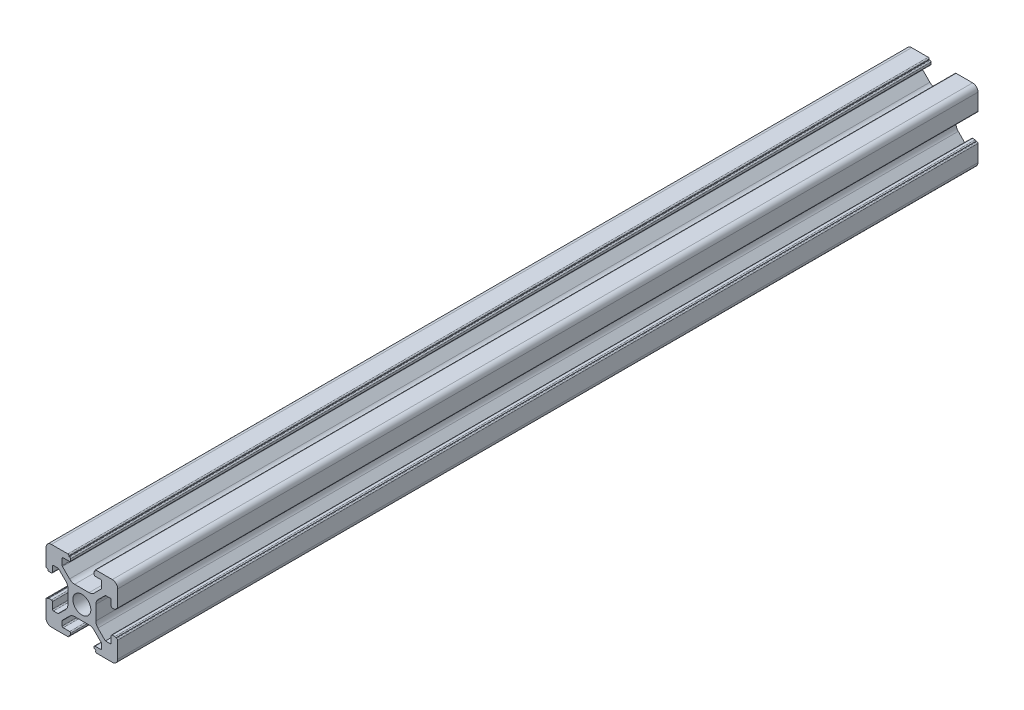
SolidWorks part; units mm, degrees
ref_plane "Front Plane" through (0, 0, 0) normal (0, 0, 1) x (1, 0, 0)
ref_plane "Top Plane" through (0, 0, 0) normal (0, 1, 0) x (1, 0, 0)
ref_plane "Right Plane" through (0, 0, 0) normal (1, 0, 0) x (0, 0, -1)
sketch "Model" plane through (0, 0, 0) normal (0, 0, 1) x (1, 0, 0)
  line L0 (3.9, -0.3) -> (3.9, -2.3109)
  line L1 (4.4858, -3.7251) -> (6.5607, -5.8)
  line L2 (6.5607, -5.8) -> (7.9, -5.8)
  line L3 (8.2, -5.5) -> (8.2, -3.7)
  line L4 (8.5, -3.4) -> (9.2, -3.4)
  line L5 (9.5, -3.7) -> (9.5, -3.6)
  line L6 (9.5, -3.6) -> (9.7, -3.6)
  line L7 (10, -3.9) -> (10, -8.5)
  line L8 (8.5, -10) -> (4.1583, -10)
  line L9 (3.4, -9) -> (3.4, -8.8)
  line L10 (3.7, -8.5) -> (5.2, -8.5)
  line L11 (5.5, -8.2) -> (5.5, -6.9849)
  line L12 (5.4121, -6.7728) -> (3.4251, -4.7858)
  line L13 (2.0109, -4.2) -> (0, -4.2)
  line L14 (0, -4.2) -> (-2.0109, -4.2)
  line L15 (-3.4251, -4.7858) -> (-5.4121, -6.7728)
  line L16 (-5.5, -6.9849) -> (-5.5, -8.2)
  line L17 (-5.2, -8.5) -> (-3.4, -8.5)
  line L18 (-3.1, -8.8) -> (-3.1, -9.2)
  line L19 (-3.9, -10) -> (-8.5, -10)
  line L20 (-10, -8.5) -> (-10, -3.9)
  line L21 (-9.7, -3.6) -> (-9.5, -3.6)
  line L22 (-9.5, -3.6) -> (-9.5, -3.7)
  line L23 (-9.2, -3.4) -> (-8.5, -3.4)
  line L24 (-8.2, -3.7) -> (-8.2, -5.5)
  line L25 (-7.9, -5.8) -> (-6.6849, -5.8)
  line L26 (-6.4728, -5.7121) -> (-4.4858, -3.7251)
  line L27 (-3.9, -2.3109) -> (-3.9, -0.3)
  line L28 (-3.9, -0.3) -> (-3.9, 1.7109)
  line L29 (-4.4858, 3.1251) -> (-6.4728, 5.1121)
  line L30 (-6.6849, 5.2) -> (-7.9, 5.2)
  line L31 (-8.2, 4.9) -> (-8.2, 3.4)
  line L32 (-8.5, 3.1) -> (-9.2, 3.1)
  line L33 (-9.5, 3.4) -> (-9.5, 3.6)
  line L34 (-9.5, 3.6) -> (-9.7, 3.6)
  line L35 (-10, 3.9) -> (-10, 8.5)
  line L36 (-8.5, 10) -> (-3.9, 10)
  line L37 (-3.6, 9.7) -> (-3.6, 9.5)
  line L38 (-3.6, 9.5) -> (-3.4, 9.5)
  line L39 (-3.1, 9.2) -> (-3.1, 8.7)
  line L40 (-3.4, 8.4) -> (-5.2, 8.4)
  line L41 (-5.5, 8.1) -> (-5.5, 6.3849)
  line L42 (-5.4121, 6.1728) -> (-3.4251, 4.1858)
  line L43 (-2.0109, 3.6) -> (0, 3.6)
  line L44 (0, 3.6) -> (2.0109, 3.6)
  line L45 (3.4251, 4.1858) -> (5.4121, 6.1728)
  line L46 (5.5, 6.3849) -> (5.5, 8.1)
  line L47 (5.2, 8.4) -> (3.7, 8.4)
  line L48 (3.4, 8.7) -> (3.4, 9.2)
  line L49 (3.7, 9.5) -> (3.6, 9.5)
  line L50 (3.6, 9.5) -> (3.6, 9.7)
  line L51 (3.9, 10) -> (8.5, 10)
  line L52 (10, 8.5) -> (10, 3.9)
  line L53 (9.7, 3.6) -> (9.5, 3.6)
  line L54 (9.5, 3.6) -> (9.5, 3.4)
  line L55 (9.2, 3.1) -> (8.5, 3.1)
  line L56 (8.2, 3.4) -> (8.2, 4.9)
  line L57 (7.9, 5.2) -> (6.6849, 5.2)
  line L58 (6.4728, 5.1121) -> (4.4858, 3.1251)
  line L59 (3.9, 1.7109) -> (3.9, -0.3)
  line L60 (-3.9, -0.3) -> (3.9, -0.3) construction
  line L61 (0, 3.6) -> (0, -4.2) construction
  circle A0 centre (0, -0.3) radius 2.5
  arc A1 (3.9, -2.3109) -> (4.4858, -3.7251) centre (5.9, -2.3109) ccw
  arc A2 (7.9, -5.8) -> (8.2, -5.5) centre (7.9, -5.5) ccw
  arc A3 (8.5, -3.4) -> (8.2, -3.7) centre (8.5, -3.7) ccw
  arc A4 (9.5, -3.7) -> (9.2, -3.4) centre (9.2, -3.7) ccw
  arc A5 (10, -3.9) -> (9.7, -3.6) centre (9.7, -3.9) ccw
  arc A6 (8.5, -10) -> (10, -8.5) centre (8.5, -8.5) ccw
  arc A7 (3.8833, -9.58) -> (4.1583, -10) centre (4.1583, -9.7) ccw
  arc A8 (3.8833, -9.58) -> (3.7, -9.3) centre (3.7, -9.5) ccw
  arc A9 (3.4, -9) -> (3.7, -9.3) centre (3.7, -9) ccw
  arc A10 (3.7, -8.5) -> (3.4, -8.8) centre (3.7, -8.8) ccw
  arc A11 (5.2, -8.5) -> (5.5, -8.2) centre (5.2, -8.2) ccw
  arc A12 (5.5, -6.9849) -> (5.4121, -6.7728) centre (5.2, -6.9849) ccw
  arc A13 (3.4251, -4.7858) -> (2.0109, -4.2) centre (2.0109, -6.2) ccw
  arc A14 (-2.0109, -4.2) -> (-3.4251, -4.7858) centre (-2.0109, -6.2) ccw
  arc A15 (-5.4121, -6.7728) -> (-5.5, -6.9849) centre (-5.2, -6.9849) ccw
  arc A16 (-5.5, -8.2) -> (-5.2, -8.5) centre (-5.2, -8.2) ccw
  arc A17 (-3.1, -8.8) -> (-3.4, -8.5) centre (-3.4, -8.8) ccw
  arc A18 (-3.4, -9.5) -> (-3.1, -9.2) centre (-3.4, -9.2) ccw
  arc A19 (-3.4, -9.5) -> (-3.6, -9.7) centre (-3.4, -9.7) ccw
  arc A20 (-3.9, -10) -> (-3.6, -9.7) centre (-3.9, -9.7) ccw
  arc A21 (-10, -8.5) -> (-8.5, -10) centre (-8.5, -8.5) ccw
  arc A22 (-9.7, -3.6) -> (-10, -3.9) centre (-9.7, -3.9) ccw
  arc A23 (-9.2, -3.4) -> (-9.5, -3.7) centre (-9.2, -3.7) ccw
  arc A24 (-8.2, -3.7) -> (-8.5, -3.4) centre (-8.5, -3.7) ccw
  arc A25 (-8.2, -5.5) -> (-7.9, -5.8) centre (-7.9, -5.5) ccw
  arc A26 (-6.6849, -5.8) -> (-6.4728, -5.7121) centre (-6.6849, -5.5) ccw
  arc A27 (-4.4858, -3.7251) -> (-3.9, -2.3109) centre (-5.9, -2.3109) ccw
  arc A28 (-3.9, 1.7109) -> (-4.4858, 3.1251) centre (-5.9, 1.7109) ccw
  arc A29 (-6.4728, 5.1121) -> (-6.6849, 5.2) centre (-6.6849, 4.9) ccw
  arc A30 (-7.9, 5.2) -> (-8.2, 4.9) centre (-7.9, 4.9) ccw
  arc A31 (-8.5, 3.1) -> (-8.2, 3.4) centre (-8.5, 3.4) ccw
  arc A32 (-9.5, 3.4) -> (-9.2, 3.1) centre (-9.2, 3.4) ccw
  arc A33 (-10, 3.9) -> (-9.7, 3.6) centre (-9.7, 3.9) ccw
  arc A34 (-8.5, 10) -> (-10, 8.5) centre (-8.5, 8.5) ccw
  arc A35 (-3.6, 9.7) -> (-3.9, 10) centre (-3.9, 9.7) ccw
  arc A36 (-3.1, 9.2) -> (-3.4, 9.5) centre (-3.4, 9.2) ccw
  arc A37 (-3.4, 8.4) -> (-3.1, 8.7) centre (-3.4, 8.7) ccw
  arc A38 (-5.2, 8.4) -> (-5.5, 8.1) centre (-5.2, 8.1) ccw
  arc A39 (-5.5, 6.3849) -> (-5.4121, 6.1728) centre (-5.2, 6.3849) ccw
  arc A40 (-3.4251, 4.1858) -> (-2.0109, 3.6) centre (-2.0109, 5.6) ccw
  arc A41 (2.0109, 3.6) -> (3.4251, 4.1858) centre (2.0109, 5.6) ccw
  arc A42 (5.4121, 6.1728) -> (5.5, 6.3849) centre (5.2, 6.3849) ccw
  arc A43 (5.5, 8.1) -> (5.2, 8.4) centre (5.2, 8.1) ccw
  arc A44 (3.4, 8.7) -> (3.7, 8.4) centre (3.7, 8.7) ccw
  arc A45 (3.7, 9.5) -> (3.4, 9.2) centre (3.7, 9.2) ccw
  arc A46 (3.9, 10) -> (3.6, 9.7) centre (3.9, 9.7) ccw
  arc A47 (10, 8.5) -> (8.5, 10) centre (8.5, 8.5) ccw
  arc A48 (9.7, 3.6) -> (10, 3.9) centre (9.7, 3.9) ccw
  arc A49 (9.2, 3.1) -> (9.5, 3.4) centre (9.2, 3.4) ccw
  arc A50 (8.2, 3.4) -> (8.5, 3.1) centre (8.5, 3.4) ccw
  arc A51 (8.2, 4.9) -> (7.9, 5.2) centre (7.9, 4.9) ccw
  arc A52 (6.6849, 5.2) -> (6.4728, 5.1121) centre (6.6849, 4.9) ccw
  arc A53 (4.4858, 3.1251) -> (3.9, 1.7109) centre (5.9, 1.7109) ccw
  dimension "D1" = 5
  dimension "D2" = 20
  dimension "D3" = 20
  dimension "D4" = 6.5
  dimension "D5" = 6.5
  dimension "D6" = 11
  dimension "D7" = 11
extrude "Boss-Extrude1" add sketch "Model" along normal blind 240
ref_plane "Plane-front" through (8.2, 0, 0) normal (-1, 0, 0) x (0, 0, 1)
ref_plane "Plane-back" through (-8.2, 0, 0) normal (-1, 0, 0) x (0, 0, 1)
ref_plane "Plane-bottom" through (0, -8.5, 0) normal (0, -1, 0) x (-1, 0, 0)
ref_plane "Plane-Top" through (0, 8.4, 0) normal (0, -1, 0) x (-1, 0, 0)
ref_axis "Center-Axis" through (0, -0.3, 240) along (0, 0, -1)
ref_plane "Plane-Horisont" through (0, -0.3, 0) normal (0, 1, 0) x (0, 0, -1)
ref_plane "Plane-Vertical" through (0, 0, 0) normal (-1, 0, 0) x (0, 0, -1)
equation "\"Width\"= 20mm"
equation "\"Length\"= 240mm"
equation "\"D1@Boss-Extrude1\"=\"Length\""
equation "\"Internal_hole_diameter\"= 5mm"
equation "\"Slot width\"= 6.5mm"
equation "\"D1@Model\"=\"Internal_hole_diameter\""
equation "\"D2@Model\"=\"Width\""
equation "\"D3@Model\"=\"Width\""
equation "\"D4@Model\"=\"Slot width\""
equation "\"D5@Model\"=\"Slot width\""
equation "\"Internal_Slot_width\"= 11mm"
equation "\"D6@Model\"=\"Internal_Slot_width\""
equation "\"D7@Model\"=\"Internal_Slot_width\""
